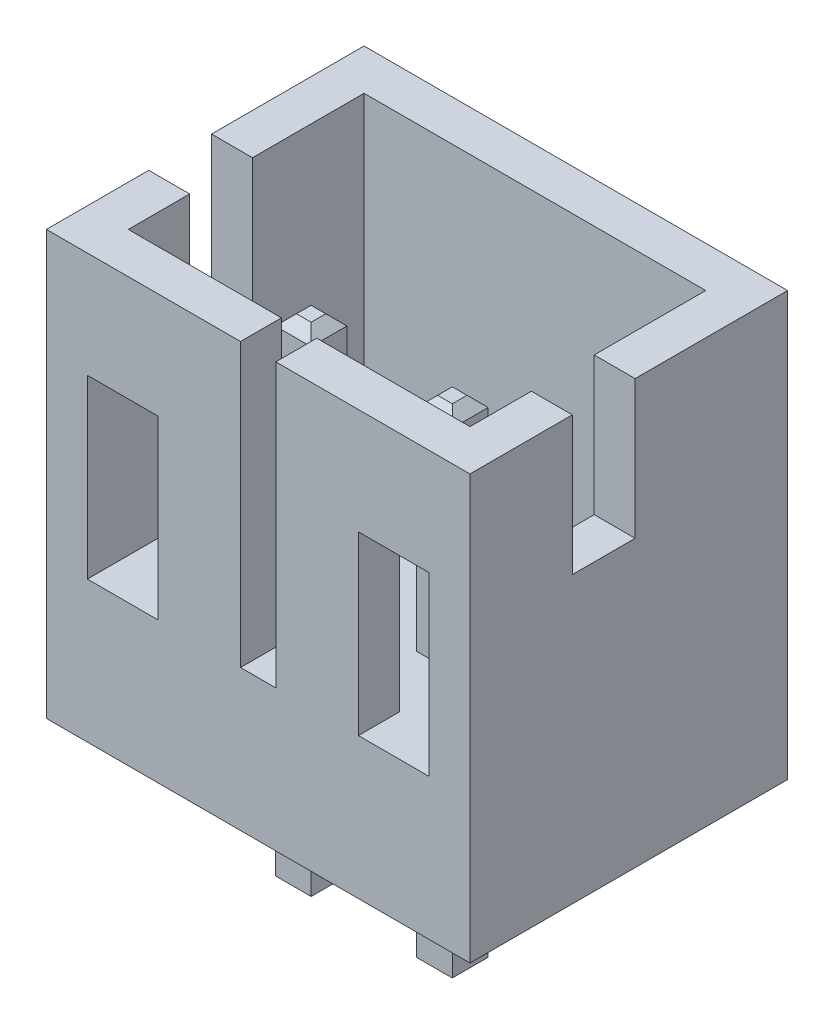
SolidWorks part; units mm, degrees
note: '?' marks a value the reader was unsure of.
ref_plane "Front Plane" through (0, 0, 0) normal (0, 0, 1) x (1, 0, 0)
ref_plane "Top Plane" through (0, 0, 0) normal (0, 1, 0) x (1, 0, 0)
ref_plane "Right Plane" through (0, 0, 0) normal (1, 0, 0) x (0, 0, -1)
sketch "Sketch4" plane through (6.8642, 0, 1.8637) normal (0, 1, 0) x (1, 0, 0)
  line L0 (-9.8642, 4.1137) -> (-3.8642, -0.3863) construction
  line L7 (-3.8642, 4.1137) -> (-9.8642, 4.1137)
  line L8 (-3.8642, 4.1137) -> (-3.8642, -0.3863)
  line L9 (-3.8642, -0.3863) -> (-9.8642, -0.3863)
  line L10 (-9.8642, 4.1137) -> (-9.8642, -0.3863)
  dimension "D4" = 6
  dimension "D7" = 4.5
extrude "Body-Extrude2" add sketch "Sketch4" along normal blind 6 separate body
shell "Body-Shell1" thickness 0.58
sketch "Sketch66" plane through (0, 0, 0) normal (1, 0, 0) x (0, 0, -1)
  line L1 (-0.8, 6) -> (-0.8, 4.04)
  line L2 (-0.8, 6) -> (0.09, 6)
  line L3 (0.09, 6) -> (0.09, 4.04)
  line L4 (-0.8, 4.04) -> (0.09, 4.04)
  line L6 (-1.67, 6) -> (1.67, 6) construction
  line L8 (-2.25, 6) -> (-2.25, 0) construction
  dimension "D1" = 0.89
  dimension "D2" = 1.96
  dimension "D3" = 1.45
extrude "Extrude3" cut sketch "Sketch66" against normal up to surface and the other way up to surface up to face at (-3, 3, 0) other way up to face at (3, 3, 0)
sketch "Sketch65" plane through (0, 0, 1.67) normal (0, 0, -1) x (1, 0, 0)
  line L0 (-2.42, -6) -> (2.42, -6) construction
  line L1 (-0.25, -6) -> (0.25, -6)
  line L2 (-0.25, -6) -> (-0.25, -2)
  line L3 (-0.25, -2) -> (0.25, -2)
  line L4 (0.25, -6) -> (0.25, -2)
  line L5 (3, -6) -> (3, 0) construction
  line L6 (-2.42, -6) -> (-2.42, -2) construction
  line L7 (-1.42, -2) -> (-2.42, -2)
  line L8 (-1.42, -2) -> (-1.42, -4.5)
  line L9 (-1.42, -4.5) -> (-2.42, -4.5)
  line L10 (-2.42, -2) -> (-2.42, -4.5)
  line L11 (-2.42, -2) -> (2.42, -2) construction
  line L12 (2.42, -6) -> (2.42, -2) construction
  line L13 (1.42, -2) -> (2.42, -2)
  line L14 (1.42, -2) -> (1.42, -4.5)
  line L15 (1.42, -4.5) -> (2.42, -4.5)
  line L16 (2.42, -2) -> (2.42, -4.5)
  point P7 (0, -2)
  dimension "D1" = 2.75
  dimension "D2" = 2.5
  dimension "D3" = 1
extrude "Extrude2" cut sketch "Sketch65" against normal up to next
ref_plane "Pins-Plane" through (0, 5.14, 0) normal (0, 1, 0) x (1, 0, 0)
sketch "Sketch64" plane through (0, 5.14, -3.64) normal (0, -1, 0) x (1, 0, 0)
  line L0 (-3, 5.89) -> (-0.25, 5.89) construction
  line L1 (0.796, 4.444) -> (1.304, 4.444)
  line L2 (0.796, 4.444) -> (0.796, 3.936)
  line L3 (0.796, 3.936) -> (1.304, 3.936)
  line L4 (1.304, 4.444) -> (1.304, 3.936)
  line L7 (3, 5.89) -> (3, 4.44) construction
  line L11 (0.796, 4.444) -> (1.304, 3.936) construction
  line L15 (1.304, 4.19) -> (-15.2685, 4.19) construction
  point P4 (1.05, 3.936)
  point P5 (3, 5.165)
  dimension "D1" = 1.7
  dimension "D2" = 0.508
  dimension "D3" = 1.95
extrude "Pins-Extrude" add sketch "Sketch64" along normal offset from surface (7.045 mm away) 1.905 up to face at (0, 0, 0) offset beyond the face yes
chamfer "Pins-Chamfer" distance 0.15 angle 45 8 edges at (1.304, -1.905, 0.55) (1.05, -1.905, 0.296) (0.796, -1.905, 0.55) (1.05, -1.905, 0.804) (0.796, 5.14, 0.55) (1.05, 5.14, 0.296) (1.304, 5.14, 0.55) (1.05, 5.14, 0.804)
pattern_linear "Pins-LPattern" count 2 spacing 2 along (-1, 0, 0) of "Pins-Extrude", "Pins-Chamfer"
ref_point "Point1"
ref_axis "Axis1" through (1.05, 5.14, 0.55) along (0, -1, 0)?
